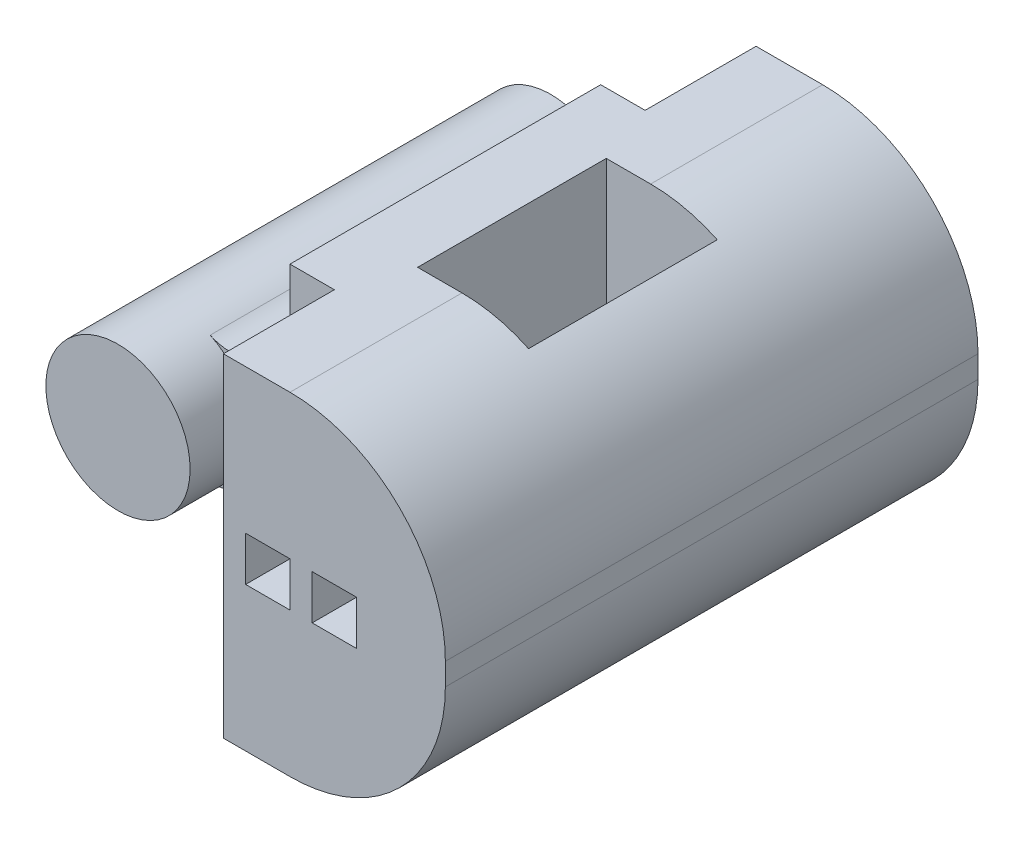
SolidWorks part; units mm, degrees
material "ABS"
ref_plane "正面" through (0, 0, 0) normal (0, 0, 1) x (1, 0, 0)
ref_plane "平面" through (0, 0, 0) normal (0, 1, 0) x (1, 0, 0)
ref_plane "右側面" through (0, 0, 0) normal (1, 0, 0) x (0, 0, -1)
sketch "ｽｹｯﾁ1" plane through (0, 0, 0) normal (0, 0, 1) x (1, 0, 0)
  circle A0 centre (0, 0) radius 3.25
  dimension "D1" = 6.5
extrude "ﾎﾞｽ - 押し出し1" add sketch "ｽｹｯﾁ1" along normal blind 19.5
ref_plane "平面1" through (5, 0, 0) normal (1, 0, 0) x (0, 0, -1)
sketch "ｽｹｯﾁ2" plane through (5, 0, 0) normal (1, 0, 0) x (0, 0, -1)
  line L0 (-19.5, 0) -> (0, 0) construction
  line L1 (-19.5, 3.25) -> (-19.5, -3.25) construction
  line L3 (-2.75, -7.5) -> (-16.75, -7.5)
  line L4 (-2.75, -7.5) -> (-2.75, 7.5)
  line L5 (-2.75, 7.5) -> (-16.75, 7.5)
  line L6 (-16.75, -7.5) -> (-16.75, 7.5)
  line L7 (-2.75, -7.5) -> (-16.75, 7.5) construction
  line L8 (-2.75, 7.5) -> (-16.75, -7.5) construction
  point P5 (-9.75, 0)
  dimension "D1" = 15
  dimension "D2" = 14
extrude "ﾎﾞｽ - 押し出し2" add sketch "ｽｹｯﾁ2" along normal blind 2 separate body
sketch "ｽｹｯﾁ3" plane through (0, 0, 2.75) normal (0, 0, -1) x (-1, 0, 0)
  line L0 (0, 0) -> (-5, 4.5)
  line L1 (-5, 3.575) -> (-5, -3.575) construction
  line L2 (-5, 4.5) -> (-5, -4.5)
  line L3 (-5, -4.5) -> (0, 0)
  dimension "D1" = 9
extrude "ﾎﾞｽ - 押し出し3" add sketch "ｽｹｯﾁ3" against normal up to surface (14 mm away) up to face at (6, 0, 16.75)
fillet "ﾌｨﾚｯﾄ1" radius 2 4 edges at (5, -4.5, 9.75) (2.4157, -2.1741, 9.75) (2.4157, 2.1741, 9.75) (5, 4.5, 9.75)
sketch "ｽｹｯﾁ5" plane through (7, 0, 0) normal (1, 0, 0) x (0, 0, -1)
  line L0 (-16.75, 0) -> (-2.75, 0) construction
  line L3 (-16.75, 7.5) -> (-16.75, -7.5) construction
  line L16 (-2.75, -2.9305) -> (-2.75, 2.9305) construction
  line L18 (-21.75, -7.5) -> (2.25, -7.5)
  line L19 (-21.75, -7.5) -> (-21.75, 7.5)
  line L20 (-21.75, 7.5) -> (2.25, 7.5)
  line L21 (2.25, -7.5) -> (2.25, 7.5)
  line L22 (-21.75, -7.5) -> (2.25, 7.5) construction
  line L23 (-21.75, 7.5) -> (2.25, -7.5) construction
  point P6 (-9.75, 0)
  dimension "D1" = 15
  dimension "D2" = 24
extrude "ﾎﾞｽ - 押し出し4" add sketch "ｽｹｯﾁ5" along normal blind 10
sketch "ｽｹｯﾁ6" plane through (17, 0, 0) normal (1, 0, 0) x (0, 0, -1)
  line L0 (-21.75, 0) -> (2.25, 0) construction
  line L1 (-21.75, 7.5) -> (-21.75, -7.5) construction
  line L2 (2.25, -7.5) -> (2.25, 7.5) construction
  line L4 (-12, -1) -> (-14, -1)
  line L5 (-12, -1) -> (-12, 1)
  line L6 (-12, 1) -> (-14, 1)
  line L7 (-14, -1) -> (-14, 1)
  line L8 (-12, -1) -> (-14, 1) construction
  line L9 (-12, 1) -> (-14, -1) construction
  line L10 (-5.5, -1) -> (-7.5, -1)
  line L11 (-5.5, -1) -> (-5.5, 1)
  line L12 (-5.5, 1) -> (-7.5, 1)
  line L13 (-7.5, -1) -> (-7.5, 1)
  line L14 (-5.5, -1) -> (-7.5, 1) construction
  line L15 (-5.5, 1) -> (-7.5, -1) construction
  point P2 (0, 0)
  point P3 (0, 0)
  point P4 (0, 0)
  point P5 (0, 0)
  point P6 (-13, 0)
  point P8 (-9.75, 0)
  point P12 (-6.5, 0)
  point P21 (0, 0)
  dimension "D1" = 3.25
  dimension "D2" = 3.25
  dimension "D3" = 2
  dimension "D4" = 2
extrude "ｶｯﾄ - 押し出し1" cut sketch "ｽｹｯﾁ6" against normal through all
sketch "ｽｹｯﾁ7" plane through (0, 0, 21.75) normal (0, 0, 1) x (1, 0, 0)
  line L0 (0, 0) -> (17, 0) construction
  line L1 (17, 7.5) -> (17, -7.5) construction
  line L2 (7, 7.5) -> (7, -7.5) construction
  line L3 (10, 1) -> (8, 1)
  line L4 (10, 1) -> (10, -1)
  line L5 (10, -1) -> (8, -1)
  line L6 (8, 1) -> (8, -1)
  line L7 (10, 1) -> (8, -1) construction
  line L8 (10, -1) -> (8, 1) construction
  line L9 (13, 1) -> (11, 1)
  line L10 (13, 1) -> (13, -1)
  line L11 (13, -1) -> (11, -1)
  line L12 (11, 1) -> (11, -1)
  line L13 (13, 1) -> (11, -1) construction
  line L14 (13, -1) -> (11, 1) construction
  point P5 (9, 0)
  point P10 (12, 0)
  dimension "D1" = 2
  dimension "D2" = 2
  dimension "D3" = 3
extrude "ｶｯﾄ - 押し出し2" cut sketch "ｽｹｯﾁ7" against normal through all
sketch "ｽｹｯﾁ8" plane through (0, 7.5, 0) normal (0, 1, 0) x (1, 0, 0)
  line L0 (-3.0923, -5.5) -> (8, -5.5) construction
  line L1 (8, -5.5) -> (13, -5.5)
  line L2 (8, -5.5) -> (8, -14)
  line L3 (8, -14) -> (13, -14)
  line L4 (13, -5.5) -> (13, -14)
  line L5 (-3.0923, -14) -> (8, -14) construction
  line L6 (8, 2.25) -> (8, -5.5) construction
  line L7 (13, 2.25) -> (13, -5.5) construction
extrude "ｶｯﾄ - 押し出し3" cut sketch "ｽｹｯﾁ8" against normal through all
sketch "ｽｹｯﾁ9" plane through (13, 0, 0) normal (-1, 0, 0) x (0, 0, 1)
  line L4 (12, -1) -> (14, -1)
  line L5 (14, -1) -> (14, 1)
  line L6 (14, 1) -> (12, 1)
  line L7 (12, 1) -> (12, -1)
  line L8 (12, -1) -> (14, -1)
  line L9 (14, -1) -> (14, 1)
  line L10 (14, 1) -> (12, 1)
  line L11 (12, 1) -> (12, -1)
  line L12 (5.5, -1) -> (7.5, -1)
  line L13 (5.5, 1) -> (5.5, -1)
  line L14 (7.5, 1) -> (5.5, 1)
  line L15 (7.5, -1) -> (7.5, 1)
  line L16 (5.5, -1) -> (7.5, -1)
  line L17 (5.5, 1) -> (5.5, -1)
  line L18 (7.5, 1) -> (5.5, 1)
  line L19 (7.5, -1) -> (7.5, 1)
  dimension "D1" = 0
  dimension "D2" = 0
extrude "ﾎﾞｽ - 押し出し5" add sketch "ｽｹｯﾁ9" against normal up to surface (4 mm away) up to face at (17, 0, 13)
fillet "ﾌｨﾚｯﾄ3" radius 7 2 edges at (17, -7.5, 9.75) (17, 7.5, 9.75)
equation "\"D2@ｽｹｯﾁ6\"=\"D1@ｽｹｯﾁ6\""
